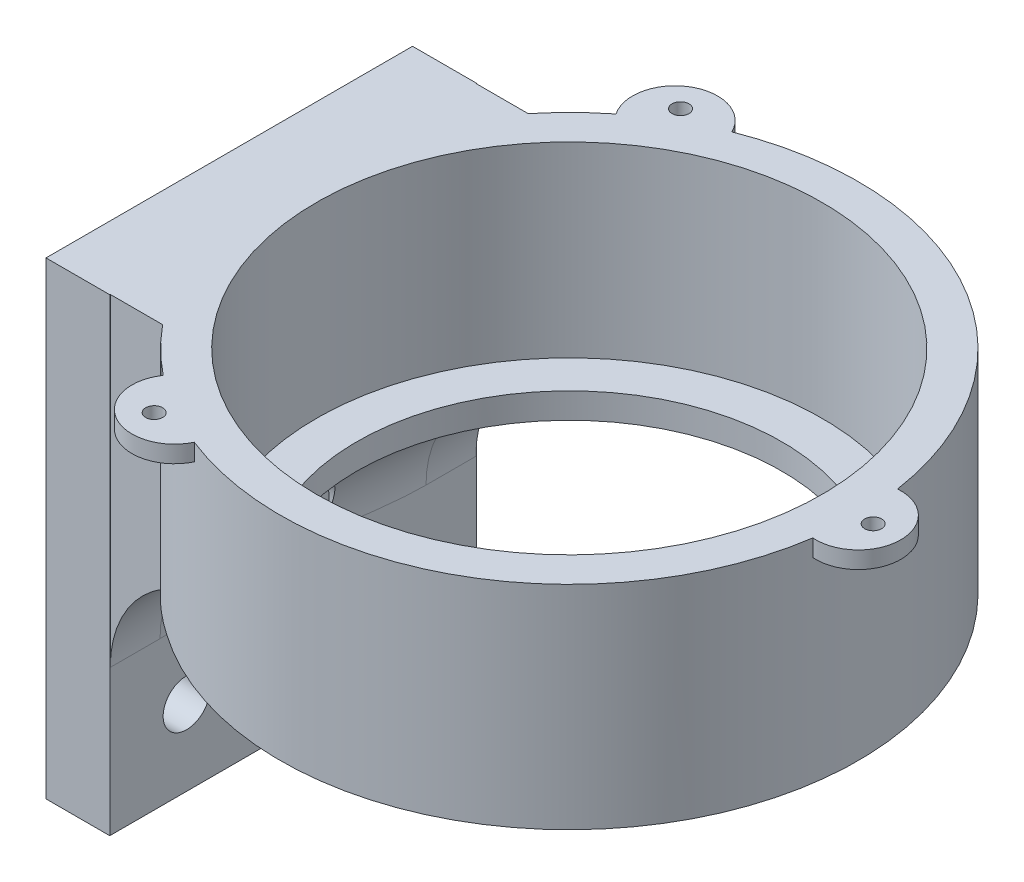
SolidWorks part; units mm, degrees
ref_plane "Front Plane" through (0, 0, 0) normal (0, 0, 1) x (1, 0, 0)
ref_plane "Top Plane" through (0, 0, 0) normal (0, 1, 0) x (1, 0, 0)
ref_plane "Right Plane" through (0, 0, 0) normal (1, 0, 0) x (0, 0, -1)
sketch "Sketch1" plane through (0, 0, 0) normal (1, 0, 0) x (0, 0, -1)
  line L1 (-21.56, -21.56) -> (21.56, -21.56)
  line L2 (-21.56, -21.56) -> (-21.56, 21.56)
  line L3 (-21.56, 21.56) -> (21.56, 21.56)
  line L4 (21.56, -21.56) -> (21.56, 21.56)
  line L5 (-21.56, -21.56) -> (21.56, 21.56) construction
  line L6 (-21.56, 21.56) -> (21.56, -21.56) construction
  circle A0 centre (-12.53, 12.53) radius 2.75 construction
  circle A1 centre (12.53, 12.53) radius 2.75 construction
  circle A2 centre (12.53, -12.53) radius 2.75
  circle A3 centre (-12.53, -12.53) radius 2.75
  point P0 (0, 0)
  dimension "D3" = 5.5
  dimension "D1" = 43.12
  dimension "D2" = 43.12
  dimension "D6" = 25.06
  dimension "D7" = 25.06
  dimension "D4" = 2
  dimension "D5" = 2
extrude "Boss-Extrude1" add sketch "Sketch1" along normal blind 7.5
sketch "Sketch3" plane through (0, 21.56, 0) normal (0, 1, 0) x (1, 0, 0)
  line L0 (0, 21.56) -> (0, -21.56) construction
  line L1 (0, 21.5) -> (13.6609, 21.5)
  line L2 (0, 21.5) -> (0, -21.5)
  line L3 (0, -21.5) -> (13.6609, -21.5)
  line L5 (13.6609, 21.5) -> (13.6609, -21.5) construction
  arc A4 (13.6609, -21.5) -> (13.6609, 21.5) centre (40, 0) ccw
  circle A8 centre (40, 0) radius 25
  dimension "D3" = 50
  dimension "D1" = 34
  dimension "D2" = 40
  dimension "D4" = 43
extrude "Boss-Extrude4" add sketch "Sketch3" against normal blind 13
sketch "Sketch8" plane through (7.5, 0, 0) normal (1, 0, 0) x (0, 0, -1)
  circle A0 centre (0, 0) radius 2.75
  dimension "D1" = 5.5
extrude "Cut-Extrude3" cut sketch "Sketch8" along normal through all both and the other way through all
ref_plane "Plane1" through (9.5, 0, 0) normal (1, 0, 0) x (0, 0, -1)
sketch "Sketch11" plane through (0, 21.56, 0) normal (0, 1, 0) x (1, 0, 0)
  circle A0 centre (40, 0) radius 29.75
  dimension "D1" = 59.5
fillet "Fillet1" radius 13 1 edges at (7.5, 8.56, 0)
sketch "Sketch13" plane through (7.5, 0, 0) normal (1, 0, 0) x (0, 0, -1)
  circle A0 centre (0, 0) radius 4.25
  dimension "D1" = 8.5
extrude "Cut-Extrude6" cut sketch "Sketch13" along normal through all
extrude "Cut-Extrude8" cut sketch "Sketch11" against normal blind 10 contours A0
sketch "Sketch15" plane through (0, 21.56, 0) normal (0, 1, 0) x (1, 0, 0)
  line L7 (7.5, -21.56) -> (7.5, -21.5)
  line L8 (7.5, -21.5) -> (13.6609, -21.5)
  line L9 (13.6609, 21.5) -> (7.5, 21.5)
  line L10 (7.5, 21.5) -> (7.5, 21.56)
  line L11 (7.5, 21.56) -> (0, 21.56)
  line L12 (0, 21.56) -> (0, -21.56)
  line L13 (0, -21.56) -> (7.5, -21.56)
  line L14 (7.5, -21.56) -> (7.5, -21.5)
  line L15 (7.5, -21.5) -> (13.6609, -21.5)
  line L16 (13.6609, 21.5) -> (7.5, 21.5)
  line L17 (7.5, 21.5) -> (7.5, 21.56)
  line L18 (7.5, 21.56) -> (0, 21.56)
  line L19 (0, 21.56) -> (0, -21.56)
  line L20 (0, -21.56) -> (7.5, -21.56)
  circle A0 centre (40, 0) radius 29.75 construction
  arc A1 (13.6609, -21.5) -> (13.6609, 21.5) centre (40, 0) ccw
  arc A2 (13.6609, -21.5) -> (13.6609, 21.5) centre (40, 0) ccw
  circle A3 centre (40, 0) radius 29.75
  dimension "D1" = 0
extrude "Boss-Extrude7" add sketch "Sketch15" along normal blind 12
sketch "Sketch16" plane through (0, 33.56, 0) normal (0, 1, 0) x (1, 0, 0)
  arc A0 (13.6609, -21.5) -> (13.6609, 21.5) centre (40, 0) ccw construction
  arc A1 (18.8654, -26.6332) -> (27.5022, -31.6197) centre (40, 0) ccw construction
  arc A2 (73.6324, 4.9865) -> (73.6324, -4.9865) centre (74, 0) cw
  arc A3 (73.6324, -4.9865) -> (73.6324, 4.9865) centre (74, 0) ccw construction
  circle A4 centre (75.75, 0) radius 1
  arc A5 (27.5022, -31.6197) -> (18.8654, -26.6332) centre (23, -29.4449) cw
  circle A6 centre (22.125, -30.9604) radius 1
  arc A7 (18.8654, 26.6332) -> (27.5022, 31.6197) centre (23, 29.4449) cw
  circle A8 centre (22.125, 30.9604) radius 1
  arc A9 (27.5022, 31.6197) -> (18.8654, 26.6332) centre (40, 0) ccw
  arc A10 (27.5022, 31.6197) -> (18.8654, 26.6332) centre (40, 0) ccw construction
  arc A11 (18.8654, -26.6332) -> (27.5022, -31.6197) centre (40, 0) ccw
  arc A12 (73.6324, -4.9865) -> (73.6324, 4.9865) centre (40, 0) ccw construction
  arc A13 (73.6324, -4.9865) -> (73.6324, 4.9865) centre (40, 0) ccw
  dimension "D1" = 2
  dimension "D2" = 3
extrude "Boss-Extrude8" add sketch "Sketch16" against normal blind 2
